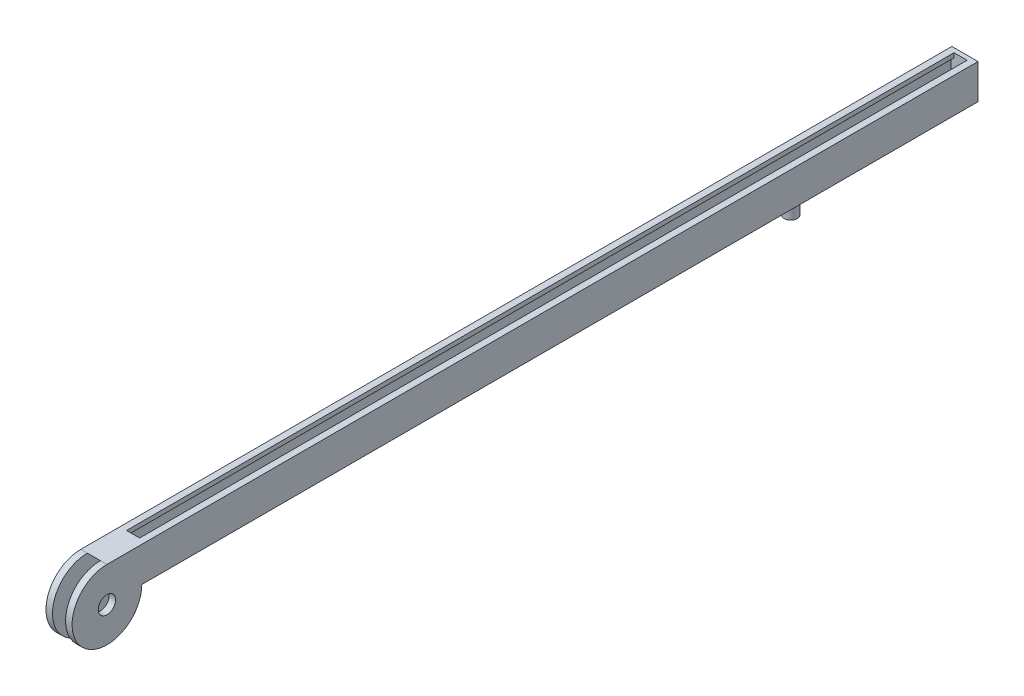
SolidWorks part; units mm, degrees
ref_plane "Front Plane" through (0, 0, 0) normal (0, 0, 1) x (1, 0, 0)
ref_plane "Top Plane" through (0, 0, 0) normal (0, 1, 0) x (1, 0, 0)
ref_plane "Right Plane" through (0, 0, 0) normal (1, 0, 0) x (0, 0, -1)
sketch "Sketch1" plane through (0, 0, 0) normal (0, 1, 0) x (1, 0, 0)
  line L0 (0, 0) -> (60, 0)
  line L1 (60, 0) -> (60, 2000)
  line L2 (60, 2000) -> (0, 2000)
  line L3 (0, 2000) -> (0, 0)
  dimension "D1" = 60
  dimension "D2" = 2000
extrude "Boss-Extrude1" add sketch "Sketch1" along normal blind 80
sketch "Sketch2" plane through (0, 0, 0) normal (0, 0, 1) x (1, 0, 0)
  line L0 (0, 80) -> (15, 80)
  line L1 (0, 80) -> (60, 80) construction
  line L2 (15, 80) -> (15, 70)
  line L3 (15, 70) -> (8, 70)
  line L4 (8, 70) -> (8, 10)
  line L5 (8, 10) -> (52, 10)
  line L6 (52, 10) -> (52, 70)
  line L7 (52, 70) -> (45, 70)
  line L8 (45, 70) -> (45, 80)
  line L9 (60, 80) -> (60, 0) construction
  line L10 (0, 0) -> (60, 0) construction
  line L11 (0, 80) -> (0, 0) construction
  line L12 (15, 80) -> (45, 80)
  dimension "D1" = 15
  dimension "D2" = 15
  dimension "D3" = 10
  dimension "D4" = 10
  dimension "D5" = 8
extrude "Cut-Extrude1" cut sketch "Sketch2" against normal blind 1900 from offset 90 contours L12 L8 L7 L6 L5 L4 L3 L2 offset against normal yes
sketch "Sketch3" plane through (60, 0, 0) normal (1, 0, 0) x (0, 0, -1)
  circle A0 centre (0, 0) radius 80
extrude "Boss-Extrude2" add sketch "Sketch3" against normal up to surface (60 mm away) up to face at (0, 40, -1000)
extrude "Cut-Extrude2" cut sketch "Sketch3<2>" against normal blind 30 from offset 15 offset against normal yes
sketch "Sketch3<2>" plane through (60, 0, 0) normal (1, 0, 0) x (0, 0, -1) same geometry as "Sketch3"
sketch "Sketch4" plane through (60, 0, 0) normal (1, 0, 0) x (0, 0, -1)
  circle A0 centre (0, 0) radius 20
  dimension "D1" = 40
extrude "Cut-Extrude3" cut sketch "Sketch4" against normal up to surface (60 mm away) up to face at (0, 15.8579, -995.8579)
sketch "Sketch5" plane through (0, 0, 0) normal (0, -1, 0) x (1, 0, 0)
  line L0 (60, -2000) -> (0, -2000) construction
  line L3 (0, -2000) -> (0, -80) construction
  circle A0 centre (30, -1600) radius 15
  circle A1 centre (30, -1600) radius 7.5
  dimension "D1" = 30
  dimension "D4" = 7.5
  dimension "D2" = 400
  dimension "D3" = 30
extrude "Boss-Extrude3" add sketch "Sketch5" along normal blind 40
sketch "Sketch6" plane through (0, -40, 0) normal (0, -1, 0) x (1, 0, 0)
  line L0 (30, -1610.5) -> (30, -1589.5) construction
  circle A0 centre (30, -1600) radius 10.5
  circle A1 centre (30, -1600) radius 15 construction
  dimension "D1" = 4.5
extrude "Cut-Extrude4" cut sketch "Sketch6" against normal blind 2 from offset 15 offset against normal yes
